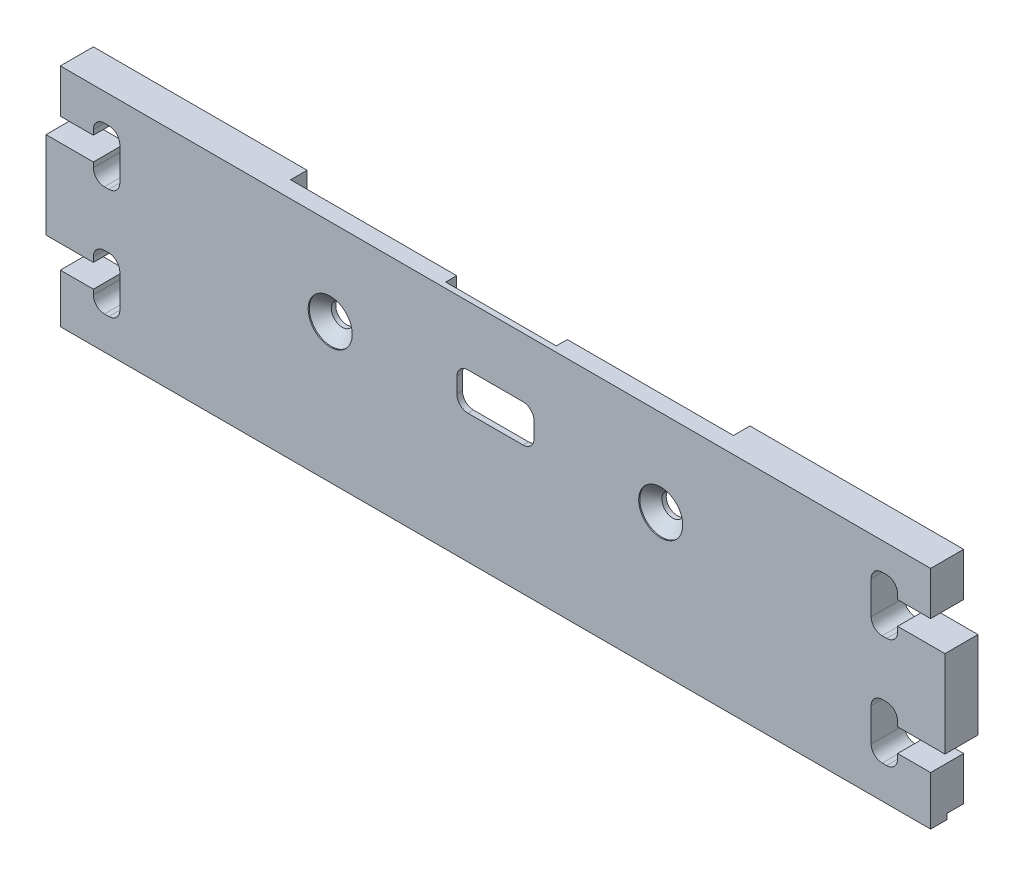
SolidWorks part; units mm, degrees
ref_plane "Front Plane" through (0, 0, 0) normal (0, 0, 1) x (1, 0, 0)
ref_plane "Top Plane" through (0, 0, 0) normal (0, 1, 0) x (1, 0, 0)
ref_plane "Right Plane" through (0, 0, 0) normal (1, 0, 0) x (0, 0, -1)
sketch "Sketch1" plane through (0, 0, 0) normal (0, 0, 1) x (1, 0, 0)
  line L0 (-39.5, 0) -> (39.5, 0) construction
  line L1 (-39.5, 10) -> (39.5, 10)
  line L2 (-39.5, 10) -> (-39.5, -10)
  line L3 (-39.5, -10) -> (39.5, -10)
  line L4 (39.5, 10) -> (39.5, -10)
  line L5 (-39.5, 10) -> (39.5, -10) construction
  line L6 (-39.5, -10) -> (39.5, 10) construction
  line L7 (0, 10) -> (0, -10) construction
  line L9 (-40.8, -3.95) -> (-39.5, -3.95)
  line L10 (-40.8, -3.95) -> (-40.8, 3.95)
  line L11 (-40.8, 3.95) -> (-39.5, 3.95)
  line L12 (-39.5, -3.95) -> (-39.5, 3.95)
  line L13 (-40.8, -3.95) -> (-39.5, 3.95) construction
  line L14 (-40.8, 3.95) -> (-39.5, -3.95) construction
  line L16 (40.8, 3.95) -> (39.5, 3.95)
  line L17 (40.8, -3.95) -> (40.8, 3.95)
  line L18 (40.8, -3.95) -> (39.5, -3.95)
  line L19 (-39.5, 5) -> (39.5, 5) construction
  line L20 (-35.3, 7.5) -> (-35.3, 2.5) construction
  line L21 (-36.5, 3.95) -> (-39.5, 3.95)
  line L22 (-36.5, 3.95) -> (-36.5, 6.05)
  line L23 (-36.5, 6.05) -> (-39.5, 6.05)
  line L24 (-39.5, 3.95) -> (-39.5, 6.05)
  line L25 (-36.5, 3.95) -> (-39.5, 6.05) construction
  line L26 (-36.5, 6.05) -> (-39.5, 3.95) construction
  line L27 (-34.1, 7.5) -> (-36.5, 7.5)
  line L28 (-34.1, 7.5) -> (-34.1, 2.5)
  line L29 (-34.1, 2.5) -> (-36.5, 2.5)
  line L30 (-36.5, 7.5) -> (-36.5, 2.5)
  line L31 (-34.1, 7.5) -> (-36.5, 2.5) construction
  line L32 (-34.1, 2.5) -> (-36.5, 7.5) construction
  line L33 (-34.1, -7.5) -> (-36.5, -7.5)
  line L34 (-34.1, -7.5) -> (-34.1, -2.5)
  line L35 (-34.1, -2.5) -> (-36.5, -2.5)
  line L36 (-36.5, -7.5) -> (-36.5, -2.5)
  line L37 (-36.5, -3.95) -> (-39.5, -3.95)
  line L38 (-36.5, -6.05) -> (-39.5, -6.05)
  line L39 (36.5, 3.95) -> (39.5, 3.95)
  line L40 (36.5, 6.05) -> (39.5, 6.05)
  line L41 (36.5, 7.5) -> (36.5, 2.5)
  line L42 (34.1, 7.5) -> (36.5, 7.5)
  line L43 (34.1, 7.5) -> (34.1, 2.5)
  line L44 (34.1, 2.5) -> (36.5, 2.5)
  line L45 (34.1, -2.5) -> (36.5, -2.5)
  line L46 (34.1, -7.5) -> (34.1, -2.5)
  line L47 (34.1, -7.5) -> (36.5, -7.5)
  line L48 (36.5, -7.5) -> (36.5, -2.5)
  line L49 (36.5, -6.05) -> (39.5, -6.05)
  line L50 (36.5, -3.95) -> (39.5, -3.95)
  point P0 (0, 0)
  point P10 (-40.15, 0)
  point P15 (-38, 5)
  point P35 (-35.3, 5)
  dimension "D1" = 79
  dimension "D2" = 20
  dimension "D4" = 1.3
  dimension "D7" = 5
  dimension "D8" = 2.1
  dimension "D9" = 3
  dimension "D10" = 2.4
  dimension "D11" = 5
extrude "Base shape" add sketch "Sketch1" along normal blind 3 contours L4 L1 L2 L3 | L9 L2 L11 L10 | L16 L4 L18 L17 region at (0, 0, 0) region at (-40.15, 0, 0) region at (40.15, 0, 0)
sketch "Sketch4" plane through (0, -10, 0) normal (0, -1, 0) x (1, 0, 0)
  line L0 (39.5, 3) -> (39.5, 0) construction
  line L1 (-39.5, 3) -> (39.5, 3)
  line L2 (-39.5, 3) -> (-39.5, 1.5)
  line L3 (-39.5, 1.5) -> (39.5, 1.5)
  line L4 (39.5, 3) -> (39.5, 1.5)
extrude "Floor lip" add sketch "Sketch4" along normal blind 0.5
sketch "Sketch6" plane through (0, 0, 0) normal (0, 0, -1) x (-1, 0, 0)
  line L0 (0, 0) -> (0, -10) construction
  line L1 (39.5, -10) -> (-39.5, -10) construction
  line L2 (-4, -10) -> (4, -10) construction
  line L3 (39.5, -10) -> (-39.5, -10) construction
  line L4 (-4, -9) -> (4, -9)
  line L5 (-4, -11) -> (4, -11)
  arc A0 (-4, -9) -> (-4, -11) centre (-4, -10) ccw
  arc A1 (4, -11) -> (4, -9) centre (4, -10) ccw
  point P9 (0, -10)
  dimension "D1" = 2
  dimension "D2" = 8
extrude "Nail cutout" cut sketch "Sketch6" against normal up to surface (1.5 mm away) up to face at (0, -10.25, 1.5)
sketch "Sketch3" plane through (-40.8, 0, 0) normal (-1, 0, 0) x (0, 0, 1)
  line L0 (0, 6.05) -> (3, 3.95) construction
  line L1 (0, 6.05) -> (3, 6.05)
  line L2 (0, 6.05) -> (0, 3.95)
  line L3 (0, 3.95) -> (3, 3.95)
  line L4 (3, 6.05) -> (3, 3.95)
  line L5 (0, -3.95) -> (3, -6.05) construction
  line L6 (0, -3.95) -> (3, -3.95)
  line L7 (0, -3.95) -> (0, -6.05)
  line L8 (0, -6.05) -> (3, -6.05)
  line L9 (3, -3.95) -> (3, -6.05)
  point P6 (1.5, 5)
  point P13 (1.5, -5)
ref_axis "Tap axis top" through (-53.7846, 5, 1.5) along (1, 0, 0)
ref_axis "Tap axis bottom" through (-54.2844, -5, 1.5) along (1, 0, 0)
fillet "Mill fillets" radius 1 16 edges at (36.5, -7.5, 1.5) (36.5, 2.5, 1.5) (34.1, 2.5, 1.5) (34.1, -7.5, 1.5) (36.5, -2.5, 1.5) (36.5, 7.5, 1.5) (34.1, -2.5, 1.5) (34.1, 7.5, 1.5) (-36.5, -2.5, 1.5) (-34.1, -2.5, 1.5) (-34.1, -7.5, 1.5) (-36.5, -7.5, 1.5) (-36.5, 2.5, 1.5) (-34.1, 2.5, 1.5) (-34.1, 7.5, 1.5) (-36.5, 7.5, 1.5)
sketch "Sketch8" [suppressed] plane through (0, 0, 3) normal (0, 0, 1) x (1, 0, 0)
  line L0 (-40.8, 0) -> (40.8, 0) construction
  line L1 (-40.8, -3.95) -> (-40.8, 3.95) construction
  line L2 (40.8, -3.95) -> (40.8, 3.95) construction
  line L4 (-24.5, 5.15) -> (24.5, 5.15)
  line L5 (-25.5, 4.15) -> (-25.5, -4.15)
  line L6 (-24.5, -5.15) -> (24.5, -5.15)
  line L7 (25.5, 4.15) -> (25.5, -4.15)
  line L8 (-25.5, 5.15) -> (25.5, -5.15) construction
  line L9 (-25.5, -5.15) -> (25.5, 5.15) construction
  arc A0 (24.5, -5.15) -> (25.5, -4.15) centre (24.5, -4.15) ccw
  arc A1 (24.5, 5.15) -> (25.5, 4.15) centre (24.5, 4.15) cw
  arc A2 (-25.5, -4.15) -> (-24.5, -5.15) centre (-24.5, -4.15) ccw
  arc A3 (-24.5, 5.15) -> (-25.5, 4.15) centre (-24.5, 4.15) ccw
  point P6 (0, 0)
  dimension "D3" = 1
  dimension "D1" = 51
  dimension "D2" = 10.3
extrude "Led strip pocket" [suppressed] cut sketch "Sketch8" against normal offset from surface (2.5 mm away) 0.5 up to face at (0, -0.6712, 0)
sketch "Sketch9" [suppressed] plane through (0, 0, 0.5) normal (0, 0, 1) x (1, 0, 0)
  line L0 (-19.5, 5.15) -> (-19.5, -5.15)
  line L1 (0, 5.15) -> (0, -5.15) construction
  line L2 (19.5, 5.15) -> (19.5, -5.15)
  line L3 (-25.5, -2.978) -> (25.5, -2.978) construction
  line L4 (25.5, -4.15) -> (25.5, 4.15)
  line L5 (24.5, 5.15) -> (-24.5, 5.15)
  line L6 (-25.5, 4.15) -> (-25.5, -4.15)
  line L7 (-24.5, -5.15) -> (24.5, -5.15)
  line L8 (25.5, -4.15) -> (25.5, 4.15)
  line L9 (24.5, 5.15) -> (-24.5, 5.15)
  line L10 (-25.5, 4.15) -> (-25.5, -4.15)
  line L11 (-24.5, -5.15) -> (24.5, -5.15)
  circle A0 centre (-12.7, -2.978) radius 1
  circle A1 centre (12.7, -2.978) radius 1
  arc A4 (24.5, -5.15) -> (25.5, -4.15) centre (24.5, -4.15) ccw
  arc A5 (25.5, 4.15) -> (24.5, 5.15) centre (24.5, 4.15) ccw
  arc A6 (-24.5, 5.15) -> (-25.5, 4.15) centre (-24.5, 4.15) ccw
  arc A7 (-25.5, -4.15) -> (-24.5, -5.15) centre (-24.5, -4.15) ccw
  arc A8 (24.5, -5.15) -> (25.5, -4.15) centre (24.5, -4.15) ccw
  arc A9 (25.5, 4.15) -> (24.5, 5.15) centre (24.5, 4.15) ccw
  arc A10 (-24.5, 5.15) -> (-25.5, 4.15) centre (-24.5, 4.15) ccw
  arc A11 (-25.5, -4.15) -> (-24.5, -5.15) centre (-24.5, -4.15) ccw
  arc M13 (24.5, -5.15) -> (25.5, -4.15) centre (24.5, -4.15) ccw
  line M14 (25.5, -4.15) -> (25.5, 4.15)
  arc M15 (25.5, 4.15) -> (24.5, 5.15) centre (24.5, 4.15) ccw
  line M16 (24.5, 5.15) -> (-24.5, 5.15)
  arc M17 (-24.5, 5.15) -> (-25.5, 4.15) centre (-24.5, 4.15) ccw
  line M18 (-25.5, 4.15) -> (-25.5, -4.15)
  arc M19 (-25.5, -4.15) -> (-24.5, -5.15) centre (-24.5, -4.15) ccw
  line M20 (-24.5, -5.15) -> (24.5, -5.15)
  dimension "D4" = 2
  dimension "D2" = 6
  dimension "D3" = 8.128
  dimension "D5" = 25.4
  dimension "D1" = 0
extrude "Led strip cuts" [suppressed] cut sketch "Sketch9" against normal up to next contours L0 M16 M17 M18 M19 M20 | L2 M16 M20 M13 M14 M15 | A0 | A1
fillet "Led strip cut fillets" [suppressed] radius 1
sketch "Sketch13" plane through (0, 0, 0) normal (0, 0, -1) x (-1, 0, 0)
  line L0 (0, 15.8648) -> (0, -21.9195) construction
  line L2 (-4.02, -5.7) -> (4.02, -5.7)
  line L3 (-5.02, -4.7) -> (-5.02, 10)
  line L4 (-5.02, 10) -> (5.02, 10)
  line L5 (5.02, -4.7) -> (5.02, 10)
  line L6 (-5.02, -5.7) -> (5.02, 10) construction
  line L7 (-5.02, 10) -> (5.02, -5.7) construction
  line L9 (39.5, 10) -> (-39.5, 10) construction
  arc A0 (-4.02, -5.7) -> (-5.02, -4.7) centre (-4.02, -4.7) cw
  arc A1 (4.02, -5.7) -> (5.02, -4.7) centre (4.02, -4.7) ccw
  point P1 (0, 2.15)
  point P8 (0, 0)
  point P9 (5.5684, 9.0125)
  point P16 (0, 0)
  point P17 (0, 0)
  dimension "D4" = 1
  dimension "D1" = 10.04
  dimension "D2" = 15.7
extrude "Bumper mount inner cut" cut sketch "Sketch13" against normal offset from surface (2.5 mm away) 0.5 up to face at (0, -0.0192, 3)
sketch "Sketch14" plane through (0, 0, 0) normal (0, 0, -1) x (-1, 0, 0)
  line L0 (5.02, 10) -> (-5.02, 10) construction
  line L1 (0, 12.9528) -> (0, -14.0841) construction
  line L3 (-4.02, -5.7) -> (4.02, -5.7) construction
  line L4 (-20.1, 10) -> (20.1, 10)
  line L5 (-20.1, 10) -> (-20.1, -4.7)
  line L6 (-19.1, -5.7) -> (19.1, -5.7)
  line L7 (20.1, 10) -> (20.1, -4.7)
  line L8 (-20.1, 10) -> (20.1, -5.7) construction
  line L9 (-20.1, -5.7) -> (20.1, 10) construction
  arc A1 (19.1, -5.7) -> (20.1, -4.7) centre (19.1, -4.7) ccw
  arc A2 (-20.1, -4.7) -> (-19.1, -5.7) centre (-19.1, -4.7) ccw
  point P6 (0, 2.15)
  dimension "D2" = 1
  dimension "D1" = 40.2
extrude "Bumper mount outer cut" cut sketch "Sketch14" against normal blind 1.5
sketch "Sketch15" plane through (0, 0, 1.5) normal (0, 0, -1) x (-1, 0, 0)
  line L0 (-20.1, 2.15) -> (20.1, 2.15) construction
  line L3 (0, 16.4744) -> (0, -20.0474) construction
  line L4 (12.56, 10) -> (12.56, -5.7) construction
  line L5 (20.1, 10) -> (5.02, 10) construction
  line L6 (-19.1, -5.7) -> (19.1, -5.7) construction
  line L7 (-20.1, 10) -> (-20.1, -4.7) construction
  line L8 (20.1, -4.7) -> (20.1, 10) construction
  circle A0 centre (-15, 2.15) radius 1
  circle A1 centre (15, 2.15) radius 1
  point P2 (12.56, 2.15)
  point P13 (0, 0)
  point P19 (0, 0)
  dimension "D1" = 30
  dimension "D2" = 2
extrude "Bumper mount screw holes" cut sketch "Sketch15" against normal up to next
sketch "Sketch16" plane through (0, 0, 2.5) normal (0, 0, -1) x (-1, 0, 0)
  line L0 (-5.02, 2.9) -> (5.02, 2.9) construction
  line L3 (0, 10) -> (0, -4.2) construction
  line L4 (-2.5, 4.6) -> (2.5, 4.6)
  line L5 (-3.5, 3.6) -> (-3.5, 2.2)
  line L6 (-2.5, 1.2) -> (2.5, 1.2)
  line L7 (3.5, 3.6) -> (3.5, 2.2)
  line L8 (-3.5, 4.6) -> (3.5, 1.2) construction
  line L9 (-3.5, 1.2) -> (3.5, 4.6) construction
  line L11 (-5.02, 10) -> (-5.02, -4.7) construction
  line L12 (5.02, 10) -> (-5.02, 10) construction
  arc A0 (2.5, 1.2) -> (3.5, 2.2) centre (2.5, 2.2) ccw
  arc A1 (-3.5, 2.2) -> (-2.5, 1.2) centre (-2.5, 2.2) ccw
  arc A2 (-2.5, 4.6) -> (-3.5, 3.6) centre (-2.5, 3.6) ccw
  arc A3 (2.5, 4.6) -> (3.5, 3.6) centre (2.5, 3.6) cw
  point P2 (0, 0)
  point P5 (0, 0)
  point P6 (0, 2.9)
  point P23 (0, 0)
  dimension "D3" = 1
  dimension "D1" = 7
  dimension "D2" = 3.4
  dimension "D4" = 14.2
extrude "Bumper body cut" cut sketch "Sketch16" against normal up to next
hole_wizard "Bumper screw countersunks" positions "Sketch17" profile "Sketch18" countersink size "M2" standard "ANSI Metric" end condition through all
sketch "Sketch17" plane through (0, 0, 3) normal (0, 0, 1) x (1, 0, 0)
  point P0 (15, 2.15)
  point P3 (-15, 2.15)
sketch "Sketch18" plane through (15, 2.15, 3) normal (1, 0, 0) x (0, -1, 0)
  line L0 (0, 0) -> (0, 3)
  line L1 (0, 3) -> (1, 3)
  line L2 (1, 3) -> (1, 1.1)
  line L3 (1, 1.1) -> (2, 0.1)
  line L4 (2, 0.1) -> (2, 0)
  line L6 (2, 0) -> (0, 0)
  line L7 (-1, 1.1) -> (-2, 0.1) construction
  line L11 (0, -6.35) -> (0, 107.95) construction
  dimension "Thru Hole Dia." = 2
  dimension "Thru Hole Depth" = 3
  dimension "C'Sink Dia." = 4
  dimension "C'Sink Angle" = 90
  dimension "Head Clearance" = 0.1
